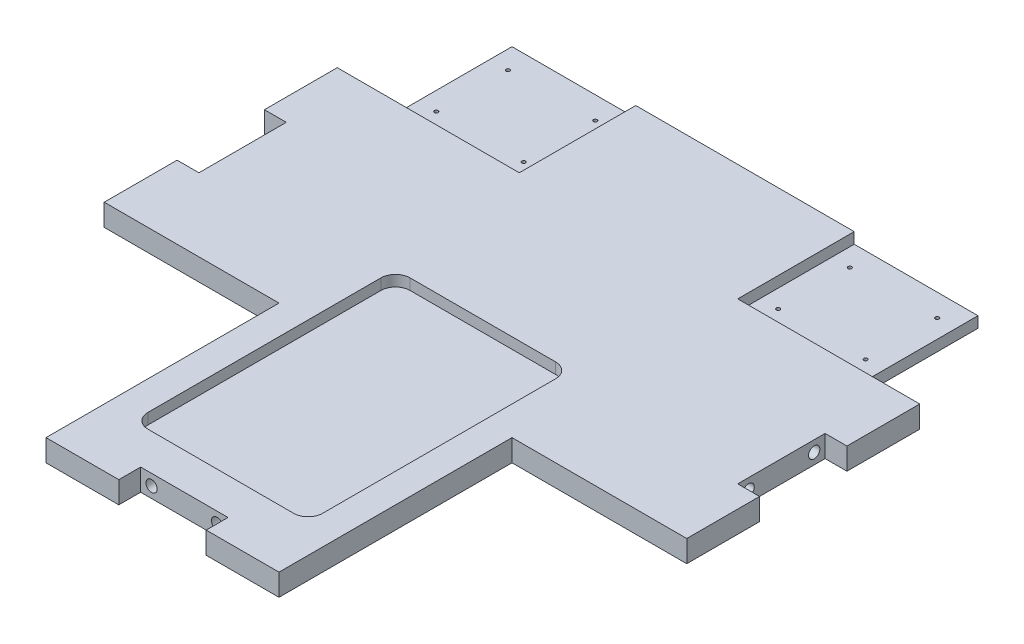
SolidWorks part; units mm, degrees
material "PE High Density"
ref_plane "Front Plane" through (0, 0, 0) normal (0, 0, 1) x (1, 0, 0)
ref_plane "Top Plane" through (0, 0, 0) normal (0, 1, 0) x (1, 0, 0)
ref_plane "Right Plane" through (0, 0, 0) normal (1, 0, 0) x (0, 0, -1)
sketch "Sketch1" plane through (0, 0, 0) normal (0, 1, 0) x (1, 0, 0)
  line L1 (-127, 127) -> (127, 127)
  line L2 (-127, 127) -> (-127, -127)
  line L3 (-127, -127) -> (127, -127)
  line L4 (127, 127) -> (127, -127)
  line L5 (-127, 127) -> (127, -127) construction
  line L6 (-127, -127) -> (127, 127) construction
  point P0 (0, 0)
  dimension "D1" = 254
  dimension "D2" = 254
extrude "Boss-Extrude1" add sketch "Sketch1" along normal blind 9.525
sketch "Sketch2" plane through (0, 9.525, 0) normal (0, 1, 0) x (1, 0, 0)
  line L0 (0, 0) -> (0, 151.7157) construction
  line L1 (-127, 127) -> (-101.6, 127)
  line L2 (-127, 127) -> (-127, 76.2)
  line L3 (-127, 76.2) -> (-101.6, 76.2)
  line L4 (-101.6, 127) -> (-101.6, 76.2)
  line L5 (127, 76.2) -> (101.6, 76.2)
  line L6 (127, 127) -> (127, 76.2)
  line L7 (127, 127) -> (101.6, 127)
  line L8 (101.6, 127) -> (101.6, 76.2)
  dimension "D1" = 50.8
  dimension "D2" = 25.4
extrude "Cut-Extrude1" cut sketch "Sketch2" against normal through all
sketch "Sketch4" plane through (0, 9.525, 0) normal (0, 1, 0) x (1, 0, 0)
  line L0 (0, 127) -> (0, 29.3179) construction
  line L1 (-101.6, 127) -> (-47.625, 127)
  line L2 (-101.6, 127) -> (-101.6, 76.2)
  line L3 (-101.6, 76.2) -> (-47.625, 76.2)
  line L4 (-47.625, 127) -> (-47.625, 76.2)
  line L5 (101.6, 127) -> (-101.6, 127) construction
  line L6 (101.6, 76.2) -> (47.625, 76.2)
  line L7 (101.6, 127) -> (101.6, 76.2)
  line L8 (101.6, 127) -> (47.625, 127)
  line L9 (47.625, 127) -> (47.625, 76.2)
  dimension "D1" = 53.975
  dimension "D2" = 50.8
extrude "Cut-Extrude2" cut sketch "Sketch4" against normal blind 4.7625
sketch "Sketch5" plane through (0, 4.7625, 0) normal (0, 1, 0) x (1, 0, 0)
  line L0 (-101.6, 101.6) -> (101.6, 101.6) construction
  line L1 (-101.6, 127) -> (-101.6, 76.2) construction
  line L2 (101.6, 76.2) -> (101.6, 127) construction
sketch "Sketch6" plane through (0, 9.525, 0) normal (0, 1, 0) x (1, 0, 0)
  line L0 (0, -127) -> (0, 26.9326) construction
  line L1 (-127, -127) -> (-50.8, -127)
  line L2 (-127, -127) -> (-127, -25.4)
  line L3 (-127, -25.4) -> (-50.8, -25.4)
  line L4 (-50.8, -127) -> (-50.8, -25.4)
  line L5 (-127, -127) -> (127, -127) construction
  line L6 (50.8, -127) -> (50.8, -25.4)
  line L7 (127, -25.4) -> (50.8, -25.4)
  line L8 (127, -127) -> (127, -25.4)
  line L9 (127, -127) -> (50.8, -127)
  dimension "D1" = 101.6
  dimension "D2" = 76.2
extrude "Cut-Extrude3" cut sketch "Sketch6" against normal through all
sketch "Sketch7" plane through (0, 9.525, 0) normal (0, 1, 0) x (1, 0, 0)
  line L0 (-127, 76.2) -> (-127, -25.4) construction
  line L1 (-127, 25.4) -> (-41.0029, 25.4) construction
  line L2 (0, 0) -> (0, -32.6591) construction
  line L3 (-127, 44.45) -> (-117.475, 44.45)
  line L4 (-127, 44.45) -> (-127, 6.35)
  line L5 (-127, 6.35) -> (-117.475, 6.35)
  line L6 (-117.475, 44.45) -> (-117.475, 6.35)
  line L7 (117.475, 44.45) -> (117.475, 6.35)
  line L8 (127, 6.35) -> (117.475, 6.35)
  line L9 (127, 44.45) -> (127, 6.35)
  line L10 (127, 44.45) -> (117.475, 44.45)
  line L11 (0, -127) -> (0, -107.95) construction
  line L13 (-19.05, -127) -> (19.05, -127)
  line L14 (-19.05, -127) -> (-19.05, -117.475)
  line L15 (-50.8, -127) -> (50.8, -127) construction
  line L16 (-19.05, -117.475) -> (19.05, -117.475)
  line L17 (19.05, -127) -> (19.05, -117.475)
  point P10 (-117.475, 25.4)
  point P27 (0, -117.475)
  dimension "D1" = 38.1
  dimension "D2" = 9.525
  dimension "D3" = 38.1
  dimension "D4" = 9.525
extrude "Cut-Extrude4" cut sketch "Sketch7" against normal through all
sketch3d "3DSketch1"
  line L0 (-117.475, 4.7625, -44.45) -> (-117.475, 4.7625, -6.35) construction
  line L1 (-117.475, 0, -44.45) -> (-117.475, 9.525, -44.45) construction
  line L2 (-117.475, 0, -6.35) -> (-117.475, 9.525, -6.35) construction
  line L3 (-19.05, 4.7625, 117.475) -> (19.05, 4.7625, 117.475) construction
  line L4 (-19.05, 0, 117.475) -> (-19.05, 9.525, 117.475) construction
  line L5 (19.05, 0, 117.475) -> (19.05, 9.525, 117.475) construction
  line L6 (117.475, 4.7625, -6.35) -> (117.475, 4.7625, -44.45) construction
  line L7 (117.475, 0, -6.35) -> (117.475, 9.525, -6.35) construction
  line L8 (117.475, 0, -44.45) -> (117.475, 9.525, -44.45) construction
  point P6 (-117.475, 4.7625, -39.6875)
  point P7 (-117.475, 4.7625, -11.1125)
  point P14 (-14.2875, 4.7625, 117.475)
  point P15 (14.2875, 4.7625, 117.475)
  point P22 (117.475, 4.7625, -11.1125)
  point P23 (117.475, 4.7625, -39.6875)
  dimension "D1" = 4.7625
  dimension "D2" = 4.7625
  dimension "D3" = 4.7625
  dimension "D4" = 4.7625
  dimension "D5" = 4.7625
  dimension "D6" = 4.7625
hole_wizard "#10 (0.1935) Diameter Hole1" positions "Sketch11" profile "Sketch10" hole size "#10" standard "ANSI Inch"
sketch "Sketch11" plane through (117.475, 0, 0) normal (1, 0, 0) x (0, 0, -1)
  point P0 (11.1125, 4.7625)
  point P3 (39.6875, 4.7625)
sketch "Sketch10" plane through (117.475, 4.7625, -11.1125) normal (0, 1, 0) x (0, 0, -1)
  line L0 (0, 0) -> (0, 14.1766)
  line L1 (0, 14.1766) -> (2.4574, 12.7)
  line L2 (2.4574, 12.7) -> (2.4574, 0)
  line L5 (2.4574, 0) -> (0, 0)
  line L10 (0, 14.1766) -> (-2.4575, 12.7) construction
  line L11 (0, -6.35) -> (0, 107.95) construction
  dimension "Hole Dia." = 4.9149
  dimension "Hole Depth" = 12.7
  dimension "Drill Angle" = 118
hole_wizard "#10 (0.1935) Diameter Hole2" positions "Sketch13" profile "Sketch12" hole size "#10" standard "ANSI Inch"
sketch "Sketch13" plane through (0, 0, 117.475) normal (0, 0, 1) x (1, 0, 0)
  point P0 (-14.2875, 4.7625)
  point P3 (14.2875, 4.7625)
sketch "Sketch12" plane through (-14.2875, 4.7625, 117.475) normal (1, 0, 0) x (0, -1, 0)
  line L0 (0, 0) -> (0, 14.1766)
  line L1 (0, 14.1766) -> (2.4574, 12.7)
  line L2 (2.4574, 12.7) -> (2.4574, 0)
  line L5 (2.4574, 0) -> (0, 0)
  line L10 (0, 14.1766) -> (-2.4575, 12.7) construction
  line L11 (0, -6.35) -> (0, 107.95) construction
  dimension "Hole Dia." = 4.9149
  dimension "Hole Depth" = 12.7
  dimension "Drill Angle" = 118
hole_wizard "#10 (0.1935) Diameter Hole3" positions "Sketch15" profile "Sketch14" hole size "#10" standard "ANSI Inch"
sketch "Sketch15" plane through (-117.475, 0, 0) normal (-1, 0, 0) x (0, 0, 1)
  point P0 (-39.6875, 4.7625)
  point P3 (-11.1125, 4.7625)
sketch "Sketch14" plane through (-117.475, 4.7625, -39.6875) normal (0, 1, 0) x (0, 0, 1)
  line L0 (0, 0) -> (0, 14.1766)
  line L1 (0, 14.1766) -> (2.4574, 12.7)
  line L2 (2.4574, 12.7) -> (2.4574, 0)
  line L5 (2.4574, 0) -> (0, 0)
  line L10 (0, 14.1766) -> (-2.4574, 12.7) construction
  line L11 (0, -6.35) -> (0, 107.95) construction
  dimension "Hole Dia." = 4.9149
  dimension "Hole Depth" = 12.7
  dimension "Drill Angle" = 118
sketch "Sketch16" plane through (0, 4.7625, 0) normal (0, 1, 0) x (1, 0, 0)
  line L0 (0, 0) -> (0, 45.1686) construction
  circle A0 centre (93.599, 117.221) radius 1.651 construction
  circle A1 centre (55.499, 117.221) radius 1.651 construction
  circle A2 centre (55.499, 85.979) radius 1.651 construction
  circle A3 centre (93.599, 85.979) radius 1.651 construction
  circle A4 centre (-55.499, 85.979) radius 1.651 construction
  circle A5 centre (-93.599, 85.979) radius 1.651 construction
  circle A6 centre (-93.599, 117.221) radius 1.651 construction
  circle A7 centre (-55.499, 117.221) radius 1.651 construction
  circle A8 centre (93.599, 117.221) radius 0.7937
  circle A9 centre (55.499, 117.221) radius 0.7937
  circle A10 centre (55.499, 85.979) radius 0.7937
  circle A11 centre (93.599, 85.979) radius 0.7937
  circle A12 centre (-93.599, 85.979) radius 1.651 construction
  circle A13 centre (-55.499, 85.979) radius 1.651 construction
  circle A14 centre (-55.499, 117.221) radius 1.651 construction
  circle A15 centre (-93.599, 117.221) radius 1.651 construction
  circle A16 centre (-93.599, 85.979) radius 0.7938
  circle A17 centre (-55.499, 85.979) radius 0.7938
  circle A18 centre (-55.499, 117.221) radius 0.7938
  circle A19 centre (-93.599, 117.221) radius 0.7938
  dimension "D1" = 1.5875
sketch "Sketch17" plane through (0, 9.525, 0) normal (0, 1, 0) x (1, 0, 0)
  line L0 (0, -117.475) -> (0, 23.0647) construction
  line L1 (19.05, -117.475) -> (-19.05, -117.475) construction
  line L2 (19.05, -127) -> (50.8, -127) construction
  line L3 (-38.1, 12.7) -> (38.1, 12.7)
  line L4 (-38.1, 12.7) -> (-38.1, -101.6)
  line L5 (-38.1, -101.6) -> (38.1, -101.6)
  line L6 (38.1, 12.7) -> (38.1, -101.6)
  line L7 (-38.1, 12.7) -> (38.1, -101.6) construction
  line L8 (-38.1, -101.6) -> (38.1, 12.7) construction
  point P5 (0, -44.45)
  dimension "D1" = 114.3
  dimension "D2" = 76.2
  dimension "D3" = 25.4
extrude "Cut-Extrude6" cut sketch "Sketch17" against normal blind 4.7625
fillet "Fillet1" radius 6.35 4 edges at (-38.1, 7.1438, 101.6) (38.1, 7.1438, 101.6) (38.1, 7.1438, -12.7) (-38.1, 7.1438, -12.7)
extrude "Cut-Extrude7" cut sketch "Sketch16" against normal through all
